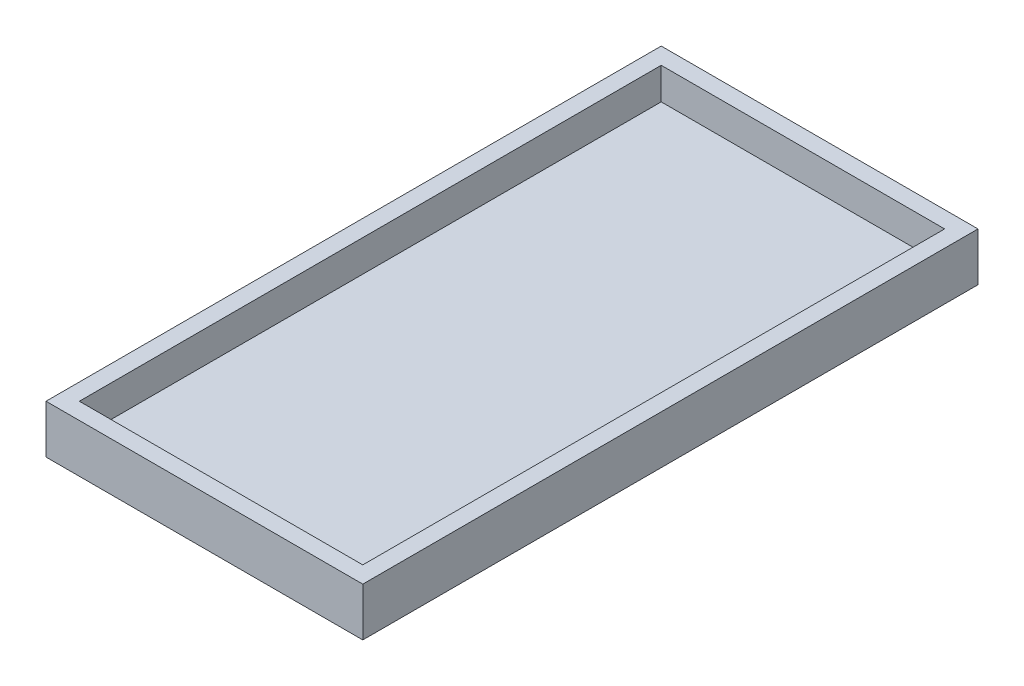
SolidWorks part; units mm, degrees
ref_plane "Front Plane" through (0, 0, 0) normal (0, 0, 1) x (1, 0, 0)
ref_plane "Top Plane" through (0, 0, 0) normal (0, 1, 0) x (1, 0, 0)
ref_plane "Right Plane" through (0, 0, 0) normal (1, 0, 0) x (0, 0, -1)
ref_axis "X-Axis" through (-88.99, 0, 0) along (1, 0, 0)
ref_axis "Y-Axis" through (0, 55, 0) along (0, -1, 0)
ref_axis "Z-Axis" through (0, 0, -88.99) along (0, 0, 1)
sketch "Sketch1" plane through (0, 0, 0) normal (0, 1, 0) x (1, 0, 0)
  line L1 (-19, -36.9) -> (19, -36.9)
  line L2 (-19, -36.9) -> (-19, 36.9)
  line L3 (-19, 36.9) -> (19, 36.9)
  line L4 (19, -36.9) -> (19, 36.9)
  line L5 (-19, -36.9) -> (19, 36.9) construction
  line L6 (-19, 36.9) -> (19, -36.9) construction
  point P0 (0, 0)
  dimension "D1" = 73.8
  dimension "D2" = 38
extrude "Boss-Extrude1" add sketch "Sketch1" along normal blind 2
sketch "Sketch2" plane through (0, 2, 0) normal (0, 1, 0) x (1, 0, 0)
  line L8 (17, -34.9) -> (17, 34.9)
  line L9 (17, 34.9) -> (-17, 34.9)
  line L10 (-17, 34.9) -> (-17, -34.9)
  line L11 (-17, -34.9) -> (17, -34.9)
  line L12 (17, -34.9) -> (17, 34.9)
  line L13 (17, 34.9) -> (-17, 34.9)
  line L14 (-17, 34.9) -> (-17, -34.9)
  line L15 (-17, -34.9) -> (17, -34.9)
  line L20 (19, -36.9) -> (19, 36.9)
  line L21 (19, 36.9) -> (-19, 36.9)
  line L22 (-19, 36.9) -> (-19, -36.9)
  line L23 (-19, -36.9) -> (19, -36.9)
  line L24 (19, -36.9) -> (19, 36.9)
  line L25 (19, 36.9) -> (-19, 36.9)
  line L26 (-19, 36.9) -> (-19, -36.9)
  line L27 (-19, -36.9) -> (19, -36.9)
  dimension "D1" = 2
  dimension "D2" = 0
extrude "Boss-Extrude2" add sketch "Sketch2" along normal blind 3.8
